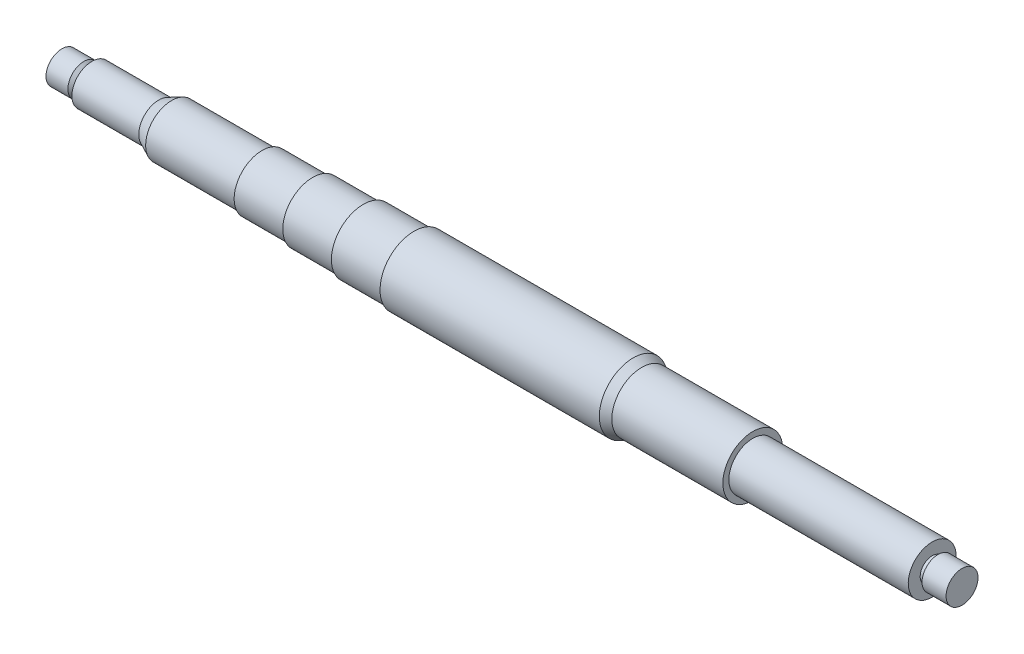
SolidWorks part; units mm, degrees
ref_plane "Front Plane" through (0, 0, 0) normal (0, 0, 1) x (1, 0, 0)
ref_plane "Top Plane" through (0, 0, 0) normal (0, 1, 0) x (1, 0, 0)
ref_plane "Right Plane" through (0, 0, 0) normal (1, 0, 0) x (0, 0, -1)
sketch "Sketch1" plane through (0, 0, 0) normal (0, 0, 1) x (1, 0, 0)
  line L0 (0, 0) -> (225.8, 0) construction
  line L4 (0, 0) -> (0, 4)
  line L5 (0, 4) -> (5.5, 4)
  line L6 (5.5, 4) -> (6.5, 3)
  line L7 (6.5, 3) -> (7.5, 3)
  line L11 (37.5, 6.5) -> (50.2, 6.5)
  line L12 (50.2, 6.5) -> (50.2, 7)
  line L13 (50.2, 7) -> (62.9, 7)
  line L14 (62.9, 7) -> (62.9, 7.5)
  line L15 (62.9, 7.5) -> (75.6, 7.5)
  line L16 (75.6, 7.5) -> (75.6, 8)
  line L17 (75.6, 8) -> (88.3, 8)
  line L18 (88.3, 8) -> (88.3, 8.5)
  line L19 (88.3, 8.5) -> (143.3, 8.5)
  line L21 (143.3, 8.5) -> (145.4445, 7.5)
  line L22 (145.4445, 7.5) -> (173.3, 7.5)
  line L23 (173.3, 7.5) -> (173.3, 6)
  line L24 (173.3, 6) -> (218.3, 6)
  line L25 (218.3, 6) -> (218.3, 3)
  line L26 (218.3, 3) -> (219.3, 3)
  line L27 (219.3, 3) -> (219.7682, 4.004)
  line L28 (219.7682, 4.004) -> (225.8, 4.004)
  line L31 (37.5, 6.5) -> (27.5, 6.5)
  line L32 (27.5, 6.5) -> (24.2832, 5)
  line L33 (24.2832, 5) -> (7.5, 5)
  line L34 (7.5, 5) -> (7.5, 3)
  line L35 (225.8, 4.004) -> (225.8, 0)
  line L36 (0, 0) -> (225.8, 0)
  dimension "D4" = 0.5
  dimension "D5" = 0.5
  dimension "D6" = 0.5
  dimension "D7" = 0.5
  dimension "D8" = 12.7
  dimension "D9" = 12.7
  dimension "D10" = 12.7
  dimension "D11" = 12.7
  dimension "D12" = 30
  dimension "D13" = 4
  dimension "D14" = 6.5
  dimension "D15" = 1
  dimension "D16" = 6
  dimension "D17" = 1
  dimension "D18" = 25
  dimension "D19" = 10
  dimension "D20" = 45
  dimension "D21" = 25
  dimension "D22" = 4.004
  dimension "D23" = 6.5
  dimension "D24" = 30
  dimension "D25" = 45
  dimension "D26" = 55
  dimension "D27" = 2
  dimension "D28" = 3
  dimension "D29" = 7.5
  dimension "D30" = 8.5
  dimension "D31" = 5
revolve "Revolve1" add sketch "Sketch1" angle 360 about L0
equation "\"Lab_Seal_Height\"= 0.089mm"
equation "\"Lab_Seal_Width\"= 12.7mm"
